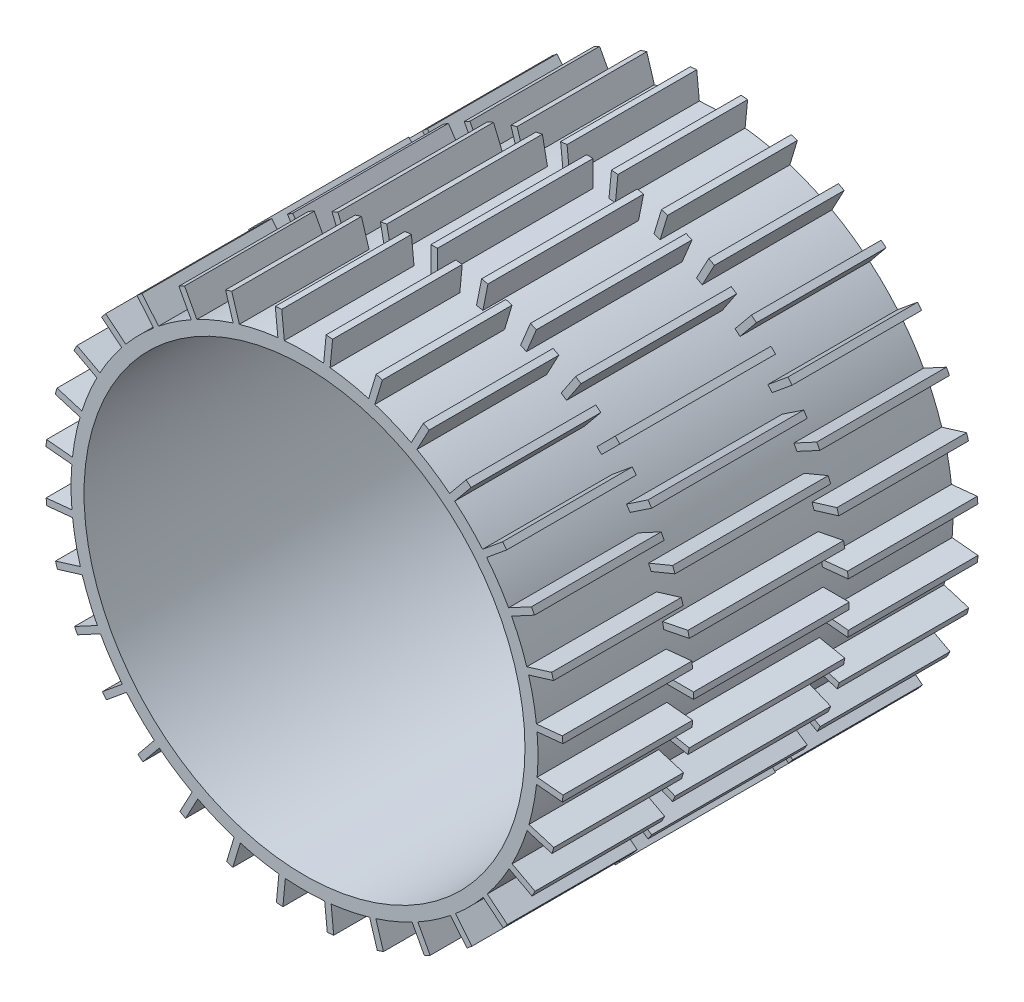
SolidWorks part; units mm, degrees
material "1060 Alloy"
ref_plane "Front Plane" through (0, 0, 0) normal (0, 0, 1) x (1, 0, 0)
ref_plane "Top Plane" through (0, 0, 0) normal (0, 1, 0) x (1, 0, 0)
ref_plane "Right Plane" through (0, 0, 0) normal (1, 0, 0) x (0, 0, -1)
sketch "Sketch1" plane through (0, 0, 0) normal (0, 0, 1) x (1, 0, 0)
  line L0 (0, 114.3) -> (0, 127)
  line L1 (1.5875, 114.289) -> (1.5875, 127)
  line L2 (-1.5875, 114.289) -> (-1.5875, 127)
  line L3 (-1.5875, 114.3) -> (-1.5875, 127) construction
  line L4 (1.5875, 114.3) -> (1.5875, 127) construction
  line L5 (-1.5875, 127) -> (1.5875, 127)
  line L6 (20.7397, 112.4027) -> (23.2195, 124.8694)
  line L7 (23.2195, 124.8694) -> (26.3335, 124.25)
  line L8 (23.8537, 111.7832) -> (26.3335, 124.25)
  line L9 (42.2698, 106.1968) -> (47.1341, 117.9402)
  line L10 (47.1341, 117.9402) -> (50.0675, 116.7252)
  line L11 (45.2032, 104.9817) -> (50.0675, 116.7252)
  line L12 (62.1756, 95.9098) -> (69.2375, 106.4786)
  line L13 (69.2375, 106.4786) -> (71.8774, 104.7147)
  line L14 (64.8155, 94.1458) -> (71.8774, 104.7147)
  line L15 (79.692, 81.937) -> (88.68, 90.9251)
  line L16 (88.68, 90.9251) -> (90.9251, 88.68)
  line L17 (81.937, 79.692) -> (90.9251, 88.68)
  line L18 (94.1458, 64.8155) -> (104.7147, 71.8774)
  line L19 (104.7147, 71.8774) -> (106.4786, 69.2375)
  line L20 (95.9098, 62.1756) -> (106.4786, 69.2375)
  line L21 (104.9817, 45.2032) -> (116.7252, 50.0675)
  line L22 (116.7252, 50.0675) -> (117.9402, 47.1341)
  line L23 (106.1968, 42.2698) -> (117.9402, 47.1341)
  line L24 (111.7832, 23.8537) -> (124.25, 26.3335)
  line L25 (124.25, 26.3335) -> (124.8694, 23.2195)
  line L26 (112.4027, 20.7397) -> (124.8694, 23.2195)
  line L27 (114.289, 1.5875) -> (127, 1.5875)
  line L28 (127, 1.5875) -> (127, -1.5875)
  line L29 (114.289, -1.5875) -> (127, -1.5875)
  line L30 (112.4027, -20.7397) -> (124.8694, -23.2195)
  line L31 (124.8694, -23.2195) -> (124.25, -26.3335)
  line L32 (111.7832, -23.8537) -> (124.25, -26.3335)
  line L33 (106.1968, -42.2698) -> (117.9402, -47.1341)
  line L34 (117.9402, -47.1341) -> (116.7252, -50.0675)
  line L35 (104.9817, -45.2032) -> (116.7252, -50.0675)
  line L36 (95.9098, -62.1756) -> (106.4786, -69.2375)
  line L37 (106.4786, -69.2375) -> (104.7147, -71.8774)
  line L38 (94.1458, -64.8155) -> (104.7147, -71.8774)
  line L39 (81.937, -79.692) -> (90.9251, -88.68)
  line L40 (90.9251, -88.68) -> (88.68, -90.9251)
  line L41 (79.692, -81.937) -> (88.68, -90.9251)
  line L42 (64.8155, -94.1458) -> (71.8774, -104.7147)
  line L43 (71.8774, -104.7147) -> (69.2375, -106.4786)
  line L44 (62.1756, -95.9098) -> (69.2375, -106.4786)
  line L45 (45.2032, -104.9817) -> (50.0675, -116.7252)
  line L46 (50.0675, -116.7252) -> (47.1341, -117.9402)
  line L47 (42.2698, -106.1968) -> (47.1341, -117.9402)
  line L48 (23.8537, -111.7832) -> (26.3335, -124.25)
  line L49 (26.3335, -124.25) -> (23.2195, -124.8694)
  line L50 (20.7397, -112.4027) -> (23.2195, -124.8694)
  line L51 (1.5875, -114.289) -> (1.5875, -127)
  line L52 (1.5875, -127) -> (-1.5875, -127)
  line L53 (-1.5875, -114.289) -> (-1.5875, -127)
  line L54 (-20.7397, -112.4027) -> (-23.2195, -124.8694)
  line L55 (-23.2195, -124.8694) -> (-26.3335, -124.25)
  line L56 (-23.8537, -111.7832) -> (-26.3335, -124.25)
  line L57 (-42.2698, -106.1968) -> (-47.1341, -117.9402)
  line L58 (-47.1341, -117.9402) -> (-50.0675, -116.7252)
  line L59 (-45.2032, -104.9817) -> (-50.0675, -116.7252)
  line L60 (-62.1756, -95.9098) -> (-69.2375, -106.4786)
  line L61 (-69.2375, -106.4786) -> (-71.8774, -104.7147)
  line L62 (-64.8155, -94.1458) -> (-71.8774, -104.7147)
  line L63 (-79.692, -81.937) -> (-88.68, -90.9251)
  line L64 (-88.68, -90.9251) -> (-90.9251, -88.68)
  line L65 (-81.937, -79.692) -> (-90.9251, -88.68)
  line L66 (-94.1458, -64.8155) -> (-104.7147, -71.8774)
  line L67 (-104.7147, -71.8774) -> (-106.4786, -69.2375)
  line L68 (-95.9098, -62.1756) -> (-106.4786, -69.2375)
  line L69 (-104.9817, -45.2032) -> (-116.7252, -50.0675)
  line L70 (-116.7252, -50.0675) -> (-117.9402, -47.1341)
  line L71 (-106.1968, -42.2698) -> (-117.9402, -47.1341)
  line L72 (-111.7832, -23.8537) -> (-124.25, -26.3335)
  line L73 (-124.25, -26.3335) -> (-124.8694, -23.2195)
  line L74 (-112.4027, -20.7397) -> (-124.8694, -23.2195)
  line L75 (-114.289, -1.5875) -> (-127, -1.5875)
  line L76 (-127, -1.5875) -> (-127, 1.5875)
  line L77 (-114.289, 1.5875) -> (-127, 1.5875)
  line L78 (-112.4027, 20.7397) -> (-124.8694, 23.2195)
  line L79 (-124.8694, 23.2195) -> (-124.25, 26.3335)
  line L80 (-111.7832, 23.8537) -> (-124.25, 26.3335)
  line L81 (-106.1968, 42.2698) -> (-117.9402, 47.1341)
  line L82 (-117.9402, 47.1341) -> (-116.7252, 50.0675)
  line L83 (-104.9817, 45.2032) -> (-116.7252, 50.0675)
  line L84 (-95.9098, 62.1756) -> (-106.4786, 69.2375)
  line L85 (-106.4786, 69.2375) -> (-104.7147, 71.8774)
  line L86 (-94.1458, 64.8155) -> (-104.7147, 71.8774)
  line L87 (-81.937, 79.692) -> (-90.9251, 88.68)
  line L88 (-90.9251, 88.68) -> (-88.68, 90.9251)
  line L89 (-79.692, 81.937) -> (-88.68, 90.9251)
  line L90 (-64.8155, 94.1458) -> (-71.8774, 104.7147)
  line L91 (-71.8774, 104.7147) -> (-69.2375, 106.4786)
  line L92 (-62.1756, 95.9098) -> (-69.2375, 106.4786)
  line L93 (-45.2032, 104.9817) -> (-50.0675, 116.7252)
  line L94 (-50.0675, 116.7252) -> (-47.1341, 117.9402)
  line L95 (-42.2698, 106.1968) -> (-47.1341, 117.9402)
  line L96 (-23.8537, 111.7832) -> (-26.3335, 124.25)
  line L97 (-26.3335, 124.25) -> (-23.2195, 124.8694)
  line L98 (-20.7397, 112.4027) -> (-23.2195, 124.8694)
  line L99 (9.3739, 113.915) -> (10.5922, 126.5675)
  line L100 (12.5343, 113.6107) -> (13.7526, 126.2632)
  line L101 (10.5922, 126.5675) -> (13.7526, 126.2632)
  line L102 (31.4175, 109.8974) -> (35.0808, 122.0691)
  line L103 (35.0808, 122.0691) -> (38.1211, 121.1541)
  line L104 (34.4578, 108.9823) -> (38.1211, 121.1541)
  line L105 (52.2537, 101.6565) -> (58.2212, 112.8796)
  line L106 (58.2212, 112.8796) -> (61.0246, 111.3891)
  line L107 (55.0571, 100.1659) -> (61.0246, 111.3891)
  line L108 (71.0819, 89.509) -> (79.1242, 99.3523)
  line L109 (79.1242, 99.3523) -> (81.5829, 97.3434)
  line L110 (73.5406, 87.5001) -> (81.5829, 97.3434)
  line L111 (87.1784, 73.9217) -> (96.9865, 82.0069)
  line L112 (96.9865, 82.0069) -> (99.0061, 79.557)
  line L113 (89.198, 71.4718) -> (99.0061, 79.557)
  line L114 (99.9247, 55.4936) -> (111.1217, 61.51)
  line L115 (111.1217, 61.51) -> (112.6245, 58.7132)
  line L116 (101.4275, 52.6968) -> (112.6245, 58.7132)
  line L117 (108.831, 34.933) -> (120.9866, 38.6493)
  line L118 (120.9866, 38.6493) -> (121.9148, 35.6131)
  line L119 (109.7592, 31.8967) -> (121.9148, 35.6131)
  line L120 (113.5549, 13.0299) -> (126.202, 14.3034)
  line L121 (126.202, 14.3034) -> (126.5201, 11.1444)
  line L122 (113.873, 9.8709) -> (126.5201, 11.1444)
  line L123 (113.915, -9.3739) -> (126.5675, -10.5922)
  line L124 (126.5675, -10.5922) -> (126.2632, -13.7526)
  line L125 (113.6107, -12.5343) -> (126.2632, -13.7526)
  line L126 (109.8974, -31.4175) -> (122.0691, -35.0808)
  line L127 (122.0691, -35.0808) -> (121.1541, -38.1211)
  line L128 (108.9823, -34.4578) -> (121.1541, -38.1211)
  line L129 (101.6565, -52.2537) -> (112.8796, -58.2212)
  line L130 (112.8796, -58.2212) -> (111.3891, -61.0246)
  line L131 (100.1659, -55.0571) -> (111.3891, -61.0246)
  line L132 (89.509, -71.0819) -> (99.3523, -79.1242)
  line L133 (99.3523, -79.1242) -> (97.3434, -81.5829)
  line L134 (87.5001, -73.5406) -> (97.3434, -81.5829)
  line L135 (73.9217, -87.1784) -> (82.0069, -96.9865)
  line L136 (82.0069, -96.9865) -> (79.557, -99.0061)
  line L137 (71.4718, -89.198) -> (79.557, -99.0061)
  line L138 (55.4936, -99.9247) -> (61.51, -111.1217)
  line L139 (61.51, -111.1217) -> (58.7132, -112.6245)
  line L140 (52.6968, -101.4275) -> (58.7132, -112.6245)
  line L141 (34.933, -108.831) -> (38.6493, -120.9866)
  line L142 (38.6493, -120.9866) -> (35.6131, -121.9148)
  line L143 (31.8967, -109.7592) -> (35.6131, -121.9148)
  line L144 (13.0299, -113.5549) -> (14.3034, -126.202)
  line L145 (14.3034, -126.202) -> (11.1444, -126.5201)
  line L146 (9.8709, -113.873) -> (11.1444, -126.5201)
  line L147 (-9.3739, -113.915) -> (-10.5922, -126.5675)
  line L148 (-10.5922, -126.5675) -> (-13.7526, -126.2632)
  line L149 (-12.5343, -113.6107) -> (-13.7526, -126.2632)
  line L150 (-31.4175, -109.8974) -> (-35.0808, -122.0691)
  line L151 (-35.0808, -122.0691) -> (-38.1211, -121.1541)
  line L152 (-34.4578, -108.9823) -> (-38.1211, -121.1541)
  line L153 (-52.2537, -101.6565) -> (-58.2212, -112.8796)
  line L154 (-58.2212, -112.8796) -> (-61.0246, -111.3891)
  line L155 (-55.0571, -100.1659) -> (-61.0246, -111.3891)
  line L156 (-71.0819, -89.509) -> (-79.1242, -99.3523)
  line L157 (-79.1242, -99.3523) -> (-81.5829, -97.3434)
  line L158 (-73.5406, -87.5001) -> (-81.5829, -97.3434)
  line L159 (-87.1784, -73.9217) -> (-96.9865, -82.0069)
  line L160 (-96.9865, -82.0069) -> (-99.0061, -79.557)
  line L161 (-89.198, -71.4718) -> (-99.0061, -79.557)
  line L162 (-99.9247, -55.4936) -> (-111.1217, -61.51)
  line L163 (-111.1217, -61.51) -> (-112.6245, -58.7132)
  line L164 (-101.4275, -52.6968) -> (-112.6245, -58.7132)
  line L165 (-108.831, -34.933) -> (-120.9866, -38.6493)
  line L166 (-120.9866, -38.6493) -> (-121.9148, -35.6131)
  line L167 (-109.7592, -31.8967) -> (-121.9148, -35.6131)
  line L168 (-113.5549, -13.0299) -> (-126.202, -14.3034)
  line L169 (-126.202, -14.3034) -> (-126.5201, -11.1444)
  line L170 (-113.873, -9.8709) -> (-126.5201, -11.1444)
  line L171 (-113.915, 9.3739) -> (-126.5675, 10.5922)
  line L172 (-126.5675, 10.5922) -> (-126.2632, 13.7526)
  line L173 (-113.6107, 12.5343) -> (-126.2632, 13.7526)
  line L174 (-109.8974, 31.4175) -> (-122.0691, 35.0808)
  line L175 (-122.0691, 35.0808) -> (-121.1541, 38.1211)
  line L176 (-108.9823, 34.4578) -> (-121.1541, 38.1211)
  line L177 (-101.6565, 52.2537) -> (-112.8796, 58.2212)
  line L178 (-112.8796, 58.2212) -> (-111.3891, 61.0246)
  line L179 (-100.1659, 55.0571) -> (-111.3891, 61.0246)
  line L180 (-89.509, 71.0819) -> (-99.3523, 79.1242)
  line L181 (-99.3523, 79.1242) -> (-97.3434, 81.5829)
  line L182 (-87.5001, 73.5406) -> (-97.3434, 81.5829)
  line L183 (-73.9217, 87.1784) -> (-82.0069, 96.9865)
  line L184 (-82.0069, 96.9865) -> (-79.557, 99.0061)
  line L185 (-71.4718, 89.198) -> (-79.557, 99.0061)
  line L186 (-55.4936, 99.9247) -> (-61.51, 111.1217)
  line L187 (-61.51, 111.1217) -> (-58.7132, 112.6245)
  line L188 (-52.6968, 101.4275) -> (-58.7132, 112.6245)
  line L189 (-34.933, 108.831) -> (-38.6493, 120.9866)
  line L190 (-38.6493, 120.9866) -> (-35.6131, 121.9148)
  line L191 (-31.8967, 109.7592) -> (-35.6131, 121.9148)
  line L192 (-13.0299, 113.5549) -> (-14.3034, 126.202)
  line L193 (-14.3034, 126.202) -> (-11.1444, 126.5201)
  line L194 (-9.8709, 113.873) -> (-11.1444, 126.5201)
  circle A0 centre (0, 0) radius 114.3
  circle A1 centre (0, 0) radius 107.95
  circle A2 centre (0, 0) radius 107.95
  circle A3 centre (0, 0) radius 107.95
  circle A4 centre (0, 0) radius 107.95
  circle A5 centre (0, 0) radius 107.95
  circle A6 centre (0, 0) radius 107.95
  circle A7 centre (0, 0) radius 107.95
  circle A8 centre (0, 0) radius 107.95
  circle A9 centre (0, 0) radius 107.95
  circle A10 centre (0, 0) radius 107.95
  circle A11 centre (0, 0) radius 107.95
  circle A12 centre (0, 0) radius 107.95
  circle A13 centre (0, 0) radius 107.95
  circle A14 centre (0, 0) radius 107.95
  circle A15 centre (0, 0) radius 107.95
  circle A16 centre (0, 0) radius 107.95
  circle A17 centre (0, 0) radius 107.95
  circle A18 centre (0, 0) radius 107.95
  circle A19 centre (0, 0) radius 107.95
  circle A20 centre (0, 0) radius 107.95
  circle A21 centre (0, 0) radius 107.95
  circle A22 centre (0, 0) radius 107.95
  circle A23 centre (0, 0) radius 107.95
  circle A24 centre (0, 0) radius 107.95
  circle A25 centre (0, 0) radius 107.95
  circle A26 centre (0, 0) radius 107.95
  circle A27 centre (0, 0) radius 107.95
  circle A28 centre (0, 0) radius 107.95
  circle A29 centre (0, 0) radius 107.95
  circle A30 centre (0, 0) radius 107.95
  circle A31 centre (0, 0) radius 107.95
  circle A32 centre (0, 0) radius 107.95
  circle A33 centre (0, 0) radius 107.95
  circle A34 centre (0, 0) radius 107.95
  circle A35 centre (0, 0) radius 107.95
  circle A36 centre (0, 0) radius 107.95
  circle A37 centre (0, 0) radius 107.95
  circle A38 centre (0, 0) radius 107.95
  circle A39 centre (0, 0) radius 107.95
  circle A40 centre (0, 0) radius 107.95
  circle A41 centre (0, 0) radius 107.95
  circle A42 centre (0, 0) radius 107.95
  circle A43 centre (0, 0) radius 107.95
  circle A44 centre (0, 0) radius 107.95
  circle A45 centre (0, 0) radius 107.95
  circle A46 centre (0, 0) radius 107.95
  circle A47 centre (0, 0) radius 107.95
  circle A48 centre (0, 0) radius 107.95
  circle A49 centre (0, 0) radius 107.95
  circle A50 centre (0, 0) radius 107.95
  circle A51 centre (0, 0) radius 107.95
  circle A52 centre (0, 0) radius 107.95
  circle A53 centre (0, 0) radius 107.95
  circle A54 centre (0, 0) radius 107.95
  circle A55 centre (0, 0) radius 107.95
  circle A56 centre (0, 0) radius 107.95
  circle A57 centre (0, 0) radius 107.95
  circle A58 centre (0, 0) radius 107.95
  circle A59 centre (0, 0) radius 107.95
  circle A60 centre (0, 0) radius 107.95
  circle A61 centre (0, 0) radius 107.95
  circle A62 centre (0, 0) radius 107.95
  circle A63 centre (0, 0) radius 107.95
  circle A64 centre (0, 0) radius 107.95
  point P169 (0, 0)
  point P175 (0, 0)
  point P332 (0, 0)
  dimension "D1" = 228.6
  dimension "D2" = 215.9
  dimension "D3" = 12.7
  dimension "D8" = 7.7864
  dimension "D4" = 1.5875
  dimension "D5" = 1.5875
  dimension "D6" = 32
  dimension "D7" = 2
  dimension "D9" = 32
extrude "Boss-Extrude1" add sketch "Sketch1" along normal blind 38.1 and the other way blind 38.1 contours A0 | A0 L0 L5 L2 | A0 L1 L5 L0 | A0 L8 L7 L6 | A0 L11 L10 L9 | A0 L14 L13 L12 | A0 L17 L16 L15 | A0 L20 L19 L18 | A0 L23 L22 L21 | A0 L26 L25 L24 | A0 L29 L28 L27 | A0 L32 L31 L30 | A0 L35 L34 L33 | A0 L38 L37 L36 | A0 L41 L40 L39 | A0 L44 L43 L42 | A0 L47 L46 L45 | A0 L50 L49 L48 | A0 L53 L52 L51 | A0 L56 L55 L54 | A0 L59 L58 L57 | A0 L62 L61 L60 | A0 L65 L64 L63 | A0 L68 L67 L66 | A0 L71 L70 L69 | A0 L74 L73 L72 | A0 L77 L76 L75 | A0 L80 L79 L78 | A0 L83 L82 L81 | A0 L86 L85 L84 | A0 L89 L88 L87 | A0 L92 L91 L90 | A0 L95 L94 L93 | A0 L98 L97 L96 region at (-0.7939, 120.6482, 0) region at (0.7939, 120.6482, 0) region at (0.7713, 111.0644, 0) region at (23.5373, 118.3299, 0) region at (-23.5373, 118.3299, 0) region at (46.1701, 111.4644, 0) region at (-46.1701, 111.4644, 0) region at (67.0285, 100.3153, 0) region at (-67.0285, 100.3153, 0) region at (85.3111, 85.3111, 0) region at (-85.3111, 85.3111, 0) region at (100.3153, 67.0285, 0) region at (-100.3153, 67.0285, 0) region at (111.4644, 46.1701, 0) region at (-111.4644, 46.1701, 0) region at (118.3299, 23.5373, 0) region at (-118.3299, 23.5373, 0) region at (120.6482, 0, 0) region at (-120.6482, 0, 0) region at (-118.3299, -23.5373, 0) region at (118.3299, -23.5373, 0) region at (-111.4644, -46.1701, 0) region at (111.4644, -46.1701, 0) region at (-100.3153, -67.0285, 0) region at (100.3153, -67.0285, 0) region at (-85.3111, -85.3111, 0) region at (85.3111, -85.3111, 0) region at (-67.0285, -100.3153, 0) region at (67.0285, -100.3153, 0) region at (-46.1701, -111.4644, 0) region at (46.1701, -111.4644, 0) region at (-23.5373, -118.3299, 0) region at (23.5373, -118.3299, 0) region at (0, -120.6482, 0)
extrude "Boss-Extrude3" add sketch "Sketch1<7>" along normal mid plane 203.2 contours A0 L167 L166 L165 | A0 | A0 L170 L169 L168 | A0 L173 L172 L171 | A0 L176 L175 L174 | A0 L179 L178 L177 | A0 L182 L181 L180 | A0 L185 L184 L183 | A0 L188 L187 L186 | A0 L191 L190 L189 | A0 L194 L193 L192 | A0 L100 L101 L99 | A0 L104 L103 L102 | A0 L107 L106 L105 | A0 L110 L109 L108 | A0 L113 L112 L111 | A0 L116 L115 L114 | A0 L119 L118 L117 | A0 L122 L121 L120 | A0 L125 L124 L123 | A0 L128 L127 L126 | A0 L131 L130 L129 | A0 L134 L133 L132 | A0 L137 L136 L135 | A0 L140 L139 L138 | A0 L143 L142 L141 | A0 L146 L145 L144 | A0 L149 L148 L147 | A0 L152 L151 L150 | A0 L155 L154 L153 | A0 L158 L157 L156 | A0 L164 L163 L162 | A0 L161 L160 L159 region at (0.7713, 111.0644, 0) region at (11.5636, 120.0927, 0) region at (-12.0875, 120.0411, 0) region at (34.7704, 115.5292, 0) region at (-35.2741, 115.3764, 0) region at (56.6409, 106.526, 0) region at (-57.1051, 106.2778, 0) region at (76.3347, 93.429, 0) region at (-76.7417, 93.0951, 0) region at (93.0951, 76.7417, 0) region at (-93.429, 76.3347, 0) region at (106.2778, 57.1051, 0) region at (-106.526, 56.6409, 0) region at (115.3764, 35.2741, 0) region at (-115.5292, 34.7704, 0) region at (120.0411, 12.0875, 0) region at (-120.0927, 11.5636, 0) region at (-120.0411, -12.0875, 0) region at (120.0927, -11.5636, 0) region at (-115.3764, -35.2741, 0) region at (115.5292, -34.7704, 0) region at (-106.2778, -57.1051, 0) region at (106.526, -56.6409, 0) region at (-93.0951, -76.7417, 0) region at (93.429, -76.3347, 0) region at (-76.3347, -93.429, 0) region at (76.7417, -93.0951, 0) region at (-56.6409, -106.526, 0) region at (57.1051, -106.2778, 0) region at (-34.7704, -115.5292, 0) region at (35.2741, -115.3764, 0) region at (-11.5636, -120.0927, 0) region at (12.0875, -120.0411, 0)
sketch "Sketch1<7>" plane through (0, 0, 0) normal (0, 0, 1) x (1, 0, 0) same geometry as "Sketch1"
extrude "Cut-Extrude1" cut sketch "Sketch1<11>" against normal mid plane 76.2 contours A0 L161 L160 L159 | A0 L164 L163 L162 | A0 L167 L166 L165 | A0 L170 L169 L168 | A0 L173 L172 L171 | A0 L176 L175 L174 | A0 L179 L178 L177 | A0 L182 L181 L180 | A0 L185 L184 L183 | A0 L188 L187 L186 | A0 L191 L190 L189 | A0 L194 L193 L192 | A0 L100 L101 L99 | A0 L104 L103 L102 | A0 L107 L106 L105 | A0 L110 L109 L108 | A0 L113 L112 L111 | A0 L116 L115 L114 | A0 L119 L118 L117 | A0 L122 L121 L120 | A0 L125 L124 L123 | A0 L128 L127 L126 | A0 L131 L130 L129 | A0 L134 L133 L132 | A0 L137 L136 L135 | A0 L140 L139 L138 | A0 L143 L142 L141 | A0 L146 L145 L144 | A0 L149 L148 L147 | A0 L152 L151 L150 | A0 L155 L154 L153 | A0 L158 L157 L156 region at (11.5636, 120.0927, 0) region at (-12.0875, 120.0411, 0) region at (34.7704, 115.5292, 0) region at (-35.2741, 115.3764, 0) region at (56.6409, 106.526, 0) region at (-57.1051, 106.2778, 0) region at (76.3347, 93.429, 0) region at (-76.7417, 93.0951, 0) region at (93.0951, 76.7417, 0) region at (-93.429, 76.3347, 0) region at (106.2778, 57.1051, 0) region at (-106.526, 56.6409, 0) region at (115.3764, 35.2741, 0) region at (-115.5292, 34.7704, 0) region at (120.0411, 12.0875, 0) region at (-120.0927, 11.5636, 0) region at (-120.0411, -12.0875, 0) region at (120.0927, -11.5636, 0) region at (-115.3764, -35.2741, 0) region at (115.5292, -34.7704, 0) region at (-106.2778, -57.1051, 0) region at (106.526, -56.6409, 0) region at (-93.0951, -76.7417, 0) region at (93.429, -76.3347, 0) region at (-76.3347, -93.429, 0) region at (76.7417, -93.0951, 0) region at (-56.6409, -106.526, 0) region at (57.1051, -106.2778, 0) region at (-34.7704, -115.5292, 0) region at (35.2741, -115.3764, 0) region at (-11.5636, -120.0927, 0) region at (12.0875, -120.0411, 0)
sketch "Sketch1<11>" plane through (0, 0, 0) normal (0, 0, 1) x (1, 0, 0) same geometry as "Sketch1"
